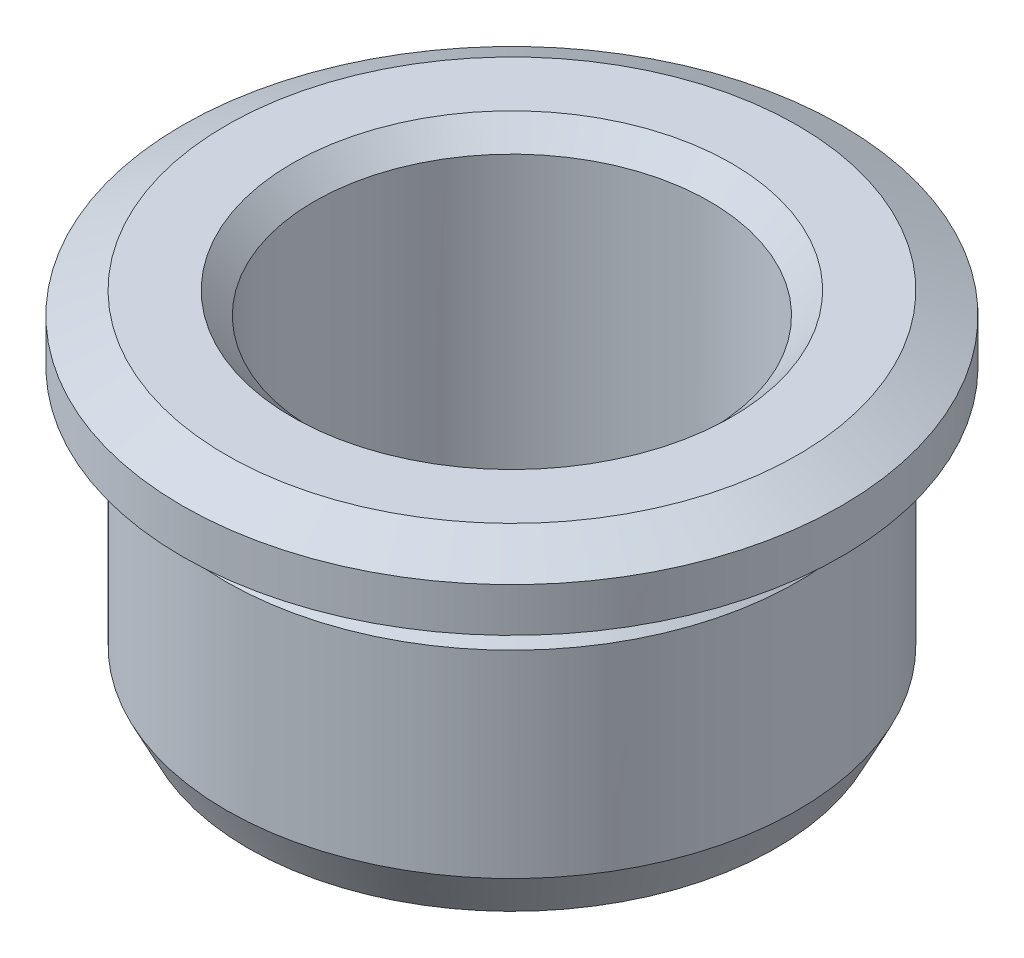
SolidWorks part; units mm, degrees
material "AISI 1020 钢，冷轧"
ref_plane "前视基准面" through (0, 0, 0) normal (0, 0, 1) x (1, 0, 0)
ref_plane "上视基准面" through (0, 0, 0) normal (0, 1, 0) x (1, 0, 0)
ref_plane "右视基准面" through (0, 0, 0) normal (1, 0, 0) x (0, 0, -1)
sketch "草图1" plane through (0, 0, 0) normal (0, 0, 1) x (1, 0, 0)
  line L0 (0, 0) -> (13, 0)
  line L1 (13, 0) -> (13, 12)
  line L2 (13, 12) -> (12, 12)
  line L3 (12, 12) -> (12, 13)
  line L4 (12, 13) -> (15, 13)
  line L5 (15, 13) -> (15, 16)
  line L6 (15, 16) -> (0, 16)
  line L7 (0, 16) -> (0, 0)
  dimension "D2" = 13
  dimension "D3" = 15
  dimension "D4" = 16
  dimension "D5" = 12
  dimension "D6" = 1
  dimension "D7" = 1
revolve "旋转1" add sketch "草图1" angle 360 about L7
sketch "草图2" plane through (0, 16, 0) normal (0, 1, 0) x (1, 0, 0)
  circle A0 centre (0, 0) radius 9
  dimension "D1" = 18
extrude "切除-拉伸1" cut sketch "草图2" against normal through all
chamfer "倒角1" distance 1 distance2 2 2 edges at (0, 0, 13) (0, 16, 15) first distance on face at (-9, 0, 0) first distance on face at (0, 16, 15)
chamfer "倒角2" distance 1 angle 45 3 edges at (-9, 16, 0) (-9, 0, 0) (0, 12, 13)
